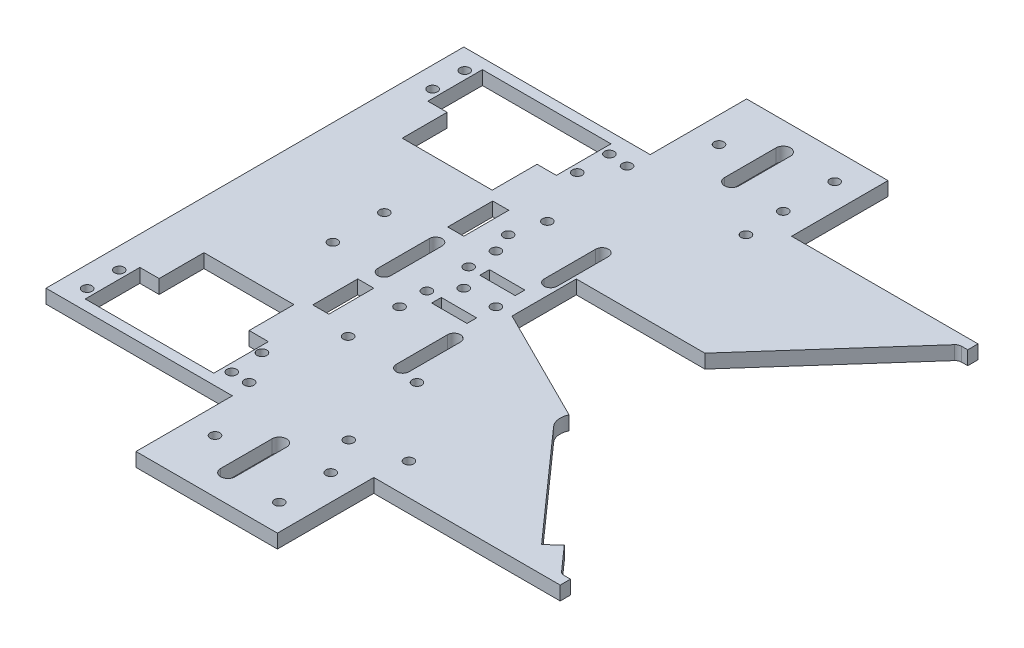
SolidWorks part; units mm, degrees
ref_plane "Front Plane" through (0, 0, 0) normal (0, 0, 1) x (1, 0, 0)
ref_plane "Top Plane" through (0, 0, 0) normal (0, 1, 0) x (1, 0, 0)
ref_plane "Right Plane" through (0, 0, 0) normal (1, 0, 0) x (0, 0, -1)
sketch "Sketch2" plane through (0, 0, 0) normal (0, 1, 0) x (1, 0, 0)
  line L2 (0, 0) -> (0, 65)
  line L3 (0, 65) -> (58, 65)
  line L4 (160, 0) -> (160, 65)
  line L8 (0, 0) -> (160, 0)
  line L9 (102, 65) -> (160, 65)
  line L11 (102, 65) -> (102, 95)
  line L12 (58, 65) -> (58, 95)
  line L13 (58, 95) -> (102, 95)
  dimension "D1" = 65
  dimension "D2" = 160
  dimension "D3" = 44
  dimension "D4" = 30
extrude "Boss-Extrude1" add sketch "Sketch2" along normal blind 4.3
mirror "Mirror1" about plane through (0, 4.3, 0) normal (0, 0, -1) of bodies 101
sketch "Sketch3" plane through (0, 4.3, 0) normal (0, 1, 0) x (1, 0, 0)
  line L0 (160, 61.8) -> (160, -61.8)
  line L1 (120.0126, 20) -> (157.1565, 61.8)
  line L3 (80.0126, 0) -> (80.0126, 20)
  line L4 (80.0126, 20) -> (120.0126, 20)
  line L12 (160, 65) -> (102, 65)
  line L13 (102, 65) -> (102, 95)
  line L15 (102, 95) -> (58, 95)
  line L16 (58, 65) -> (0, 65)
  line L17 (0, 65) -> (0, -65)
  line L18 (0, -65) -> (58, -65)
  line L20 (58, 95) -> (58, 65)
  line L22 (102, -65) -> (160, -65)
  line L23 (160, -65) -> (160, 65)
  line L36 (58, -65) -> (58, -95)
  line L38 (58, -95) -> (102, -95)
  line L39 (58, -95) -> (102, -95)
  line L40 (102, -95) -> (102, -65)
  line L42 (160, -61.8) -> (157.1556, -61.8)
  line L45 (160, 61.8) -> (157.1565, 61.8)
  line L48 (80.0126, 0) -> (120, -20)
  line L49 (120, -20) -> (157.1556, -61.8)
  line M24 (160, -65) -> (160, 65)
  dimension "D2" = 130
  dimension "D3" = 20
  dimension "D4" = 40
  dimension "D1" = 0
extrude "Cut-Extrude1" cut sketch "Sketch3" against normal blind 4.5 contours L48 L49 L1 L4 L3 M24 region at (132.7054, 4.3, -1.1594)
fillet "Fillet1" radius 2 2 edges at (157.1565, 2.15, -61.8) (157.1556, 2.15, 61.8)
ref_axis "Axis1" through (80, 4.3, 95) along (0, 0, -1)
sketch "Sketch4" plane through (0, 4.3, 0) normal (0, 1, 0) x (1, 0, 0)
  line L0 (80, -95) -> (80, 95)
  line L1 (102, -95) -> (58, -95) construction
  line L2 (102, 95) -> (58, 95) construction
ref_plane "Plane2" through (0, 4.3, 0) normal (0, 1, 0) x (1, 0, 0)
sketch "Sketch6" plane through (0, 4.3, 0) normal (0, 1, 0) x (1, 0, 0)
  line L3 (9, -61.8) -> (49, -61.8)
  line L6 (29, -45.8) -> (29, -44.8)
  line L7 (9, -44.8) -> (15, -44.8)
  line L11 (43, -44.8) -> (43, -30.8418)
  line L12 (15, -44.8) -> (15, -30.8418)
  line L13 (15, -30.8418) -> (43, -30.8418)
  line L15 (0, 0) -> (80.0126, 0)
  line L16 (80.0126, 0) -> (120, -20) construction
  line L18 (9, 44.8) -> (15, 44.8)
  line L20 (15, 30.8418) -> (43, 30.8418)
  line L21 (15, 44.8) -> (15, 30.8418)
  line L22 (43, 44.8) -> (43, 30.8418)
  line L25 (15, -45.8) -> (15, -30.8418) construction
  line L27 (9, 61.8) -> (49, 61.8)
  line L30 (4, -61.8) -> (3, -61.8)
  line L31 (0, -61.8) -> (160, -61.8) construction
  line L32 (3, -61.8) -> (4, -61.8)
  line L33 (3, -44.8) -> (3, -62.8) construction
  line L34 (3, -62.8) -> (55, -62.8) construction
  line L35 (55, -44.8) -> (55, -62.8) construction
  line L36 (4, -61.8) -> (54, -61.8) construction
  line L37 (0, 61.8) -> (160, 61.8) construction
  line L38 (54, 61.8) -> (55, 61.8)
  line L39 (54, 61.8) -> (55, 61.8)
  line L40 (43, 44.8) -> (49, 44.8)
  line L41 (4, -45.8) -> (4, -61.8) construction
  line L42 (4, -45.8) -> (54, -45.8) construction
  line L43 (43, -44.8) -> (49, -44.8)
  line L44 (3, -44.8) -> (55, -44.8) construction
  line L45 (29, -45.8) -> (29, -30.8418) construction
  line L46 (43, -45.8) -> (43, -30.8418) construction
  line L47 (54, -45.8) -> (54, -61.8) construction
  line L48 (9, -61.8) -> (49, -61.8)
  line L52 (9, 61.8) -> (9, 44.8)
  line L53 (55, 61.8) -> (54, 61.8)
  line L56 (49, 61.8) -> (49, 44.8)
  line L59 (3, -61.8) -> (4, -61.8)
  line L60 (9, -44.8) -> (9, -61.8)
  line L64 (49, -44.8) -> (49, -61.8)
  dimension "D4" = 1
  dimension "D5" = 14
  dimension "D6" = 14
extrude "Cut-Extrude2" cut sketch "Sketch6" against normal blind 10
sketch "Sketch8" plane through (0, 4.3, 0) normal (0, 1, 0) x (1, 0, 0)
  circle A0 centre (6.5, 58.8) radius 1.5
  circle A1 centre (6.5, 48.8) radius 1.5
  circle A2 centre (51.5, 48.8) radius 1.5
  circle A3 centre (51.5, 58.8) radius 1.5
  circle A4 centre (6.5, -48.7) radius 1.5
  circle A5 centre (6.5, -58.7) radius 1.5
  circle A6 centre (51.5, -58.7) radius 1.5
  circle A7 centre (51, -48.8) radius 1.5
  dimension "D7" = 3
extrude "Cut-Extrude3" cut sketch "Sketch8" against normal blind 10
sketch "Sketch9" plane through (0, 0, 0) normal (0, -1, 0) x (1, 0, 0)
  line L0 (75.75, 70.4) -> (75.75, 86.4)
  line L1 (75.75, -86.4) -> (75.75, -70.4)
  line L2 (80.25, -86.4) -> (80.25, -70.4)
  line L4 (80.25, 70.4) -> (80.25, 86.4)
  circle A0 centre (94, 70.4) radius 1.5
  circle A1 centre (66, 78.4) radius 1.5
  circle A2 centre (66, -78.4) radius 1.5
  circle A3 centre (94, -86.4) radius 1.5
  circle A4 centre (94, 86.4) radius 1.5
  circle A5 centre (94, -70.4) radius 1.5
  arc A6 (75.75, -86.4) -> (80.25, -86.4) centre (78, -86.4) ccw
  arc A7 (80.25, -70.4) -> (75.75, -70.4) centre (78, -70.4) ccw
  arc A10 (75.75, 70.4) -> (80.25, 70.4) centre (78, 70.4) ccw
  arc A12 (80.25, 86.4) -> (75.75, 86.4) centre (78, 86.4) ccw
  dimension "D1" = 3
extrude "Cut-Extrude4" cut sketch "Sketch9" against normal blind 10
sketch "Sketch7" plane through (0, 4.3, 0) normal (0, 1, 0) x (1, 0, 0)
  line L0 (0, 0) -> (80.0126, 0)
  line L1 (0, 65) -> (0, -65) construction
  line L2 (80.0126, 0) -> (80.0126, 20) construction
  line L3 (80, -95) -> (80, 95) construction
  line L4 (64, -9) -> (75, -9)
  line L5 (64, -6) -> (75, -6)
  line L6 (64, -9) -> (64, -6)
  line L7 (75, -9) -> (75, -6)
  line L8 (64, -7.5) -> (75, -7.5)
  line L9 (64, 7.5) -> (75, 7.5)
  line L10 (75, 9) -> (75, 6)
  line L11 (64, 9) -> (64, 6)
  line L12 (64, 6) -> (75, 6)
  line L13 (64, 9) -> (75, 9)
  circle A0 centre (60.0126, -6.5) radius 1.5
  circle A1 centre (60.0126, 6.5) radius 1.5
  dimension "D1" = 3
  dimension "D2" = 6.5
  dimension "D3" = 20
  dimension "D6" = 11
  dimension "D4" = 5
  dimension "D5" = 3
  dimension "D7" = 7.5
sketch "Sketch10" plane through (0, 4.3, 0) normal (0, 1, 0) x (1, 0, 0)
  line L0 (120, -20) -> (156.5589, -61.1287) construction
  line L1 (123.3218, -23.737) -> (149.8964, -53.6334)
  line L2 (116.263, -23.3218) -> (146.1593, -56.9552)
  line L3 (149.8964, -53.6334) -> (146.1593, -56.9552)
  line L4 (120, -20) -> (156.5589, -61.1287) construction
  line L5 (116.263, -23.3218) -> (152.8218, -64.4505) construction
  arc A0 (123.3218, -23.737) -> (116.263, -23.3218) centre (120, -20) ccw
  dimension "D1" = 5
  dimension "D2" = 45
extrude "Cut-Extrude5" cut sketch "Sketch10" against normal blind 10
sketch "Sketch11" plane through (0, 0, 0) normal (0, -1, 0) x (1, 0, 0)
  line L0 (0, 0) -> (80.0126, 0) construction
  line L1 (80, 95) -> (80, -95) construction
  line L2 (80.0126, 0) -> (0, 0)
  line L4 (75, 31.0313) -> (75, 15.0313)
  line L6 (79, 31.0313) -> (79, 15.0313)
  line L7 (79, -31.0313) -> (79, -15.0313)
  line L8 (75, -31.0313) -> (75, -15.0313)
  circle A0 centre (60, 31) radius 1.5
  circle A1 centre (60, 15) radius 1.5
  arc A2 (75, 31.0313) -> (79, 31.0313) centre (77, 31.0313) cw
  arc A3 (75, 15.0313) -> (79, 15.0313) centre (77, 15.0313) ccw
  arc A4 (75, -15.0313) -> (79, -15.0313) centre (77, -15.0313) cw
  arc A5 (75, -31.0313) -> (79, -31.0313) centre (77, -31.0313) ccw
  circle A6 centre (60, -15) radius 1.5
  circle A7 centre (60, -31) radius 1.5
  dimension "D1" = 3
  dimension "D2" = 16
  dimension "D3" = 15
  dimension "D4" = 20
  dimension "D5" = 15
  dimension "D6" = 4
extrude "Cut-Extrude6" cut sketch "Sketch11" against normal blind 10 contours L4 A3 L6 A2 | L8 A5 L7 A4 | A7 | A0 | A1 | A6 region at (77, 0, 23.0313) region at (77, 0, -23.0313) region at (60, 0, -31)
sketch "Sketch12" plane through (0, 0, 0) normal (0, -1, 0) x (-1, 0, 0)
  line L0 (0, 0) -> (-80.0126, 0) construction
  line L3 (-50.2627, -8) -> (-50.2627, 8)
  line L4 (-50.2627, 0) -> (-46.2627, 0)
  line L5 (-46.2627, -8) -> (-46.2627, 8)
  line L6 (0, 0) -> (-46.2627, 0)
  line L7 (0, 65) -> (0, -65) construction
  line L8 (-160, -61.8) -> (0, -61.8) construction
  line L9 (-80.0126, 0) -> (-50.2627, 0)
  line L10 (-80.0126, 0) -> (-115.5281, -17.7634) construction
  line L11 (-80.0126, 0) -> (-80.0126, 20) construction
  line L12 (-58, -65) -> (0, -65) construction
  line L13 (-58, 65) -> (0, 65) construction
  circle A0 centre (-32.2627, -8) radius 1.5
  circle A1 centre (-32.2627, 8) radius 1.5
  arc A2 (-46.2627, 8) -> (-50.2627, 8) centre (-48.2627, 8) ccw
  arc A3 (-50.2627, -8) -> (-46.2627, -8) centre (-48.2627, -8) ccw
  circle A5 centre (-32.2627, -8) radius 1.5 construction
  circle A6 centre (-32.2627, 8) radius 1.5 construction
  dimension "D1" = 3
  dimension "D8" = 8
  dimension "D9" = 8
  dimension "D2" = 8
  dimension "D3" = 14
  dimension "D4" = 4
  dimension "D5" = 61.8
  dimension "D6" = 65
  dimension "D7" = 65
extrude "Cut-Extrude7" cut sketch "Sketch12" against normal blind 10 contours A3 L5 L4 L3 | L4 L5 A2 L3 | A0 | A1 region at (48.2627, 0, 4.7958) region at (48.2627, 0, -4.7958) region at (32.2627, 0, 8) region at (32.2627, 0, -8)
extrude "Cut-Extrude8" cut sketch "Sketch7" against normal blind 9 contours A0 | L4 L7 L5 L6 | L12 L10 L13 L11 | A1
sketch "Sketch13" plane through (0, 4.3, 0) normal (0, 1, 0) x (1, 0, 0)
  line L0 (80.0126, 0) -> (59.0194, 0)
  line L1 (80, -95) -> (80, 95) construction
  circle A0 centre (65, 0) radius 1.5
  circle A1 centre (75, 0) radius 1.5
  dimension "D2" = 3
  dimension "D3" = 5
  dimension "D1" = 10
extrude "Cut-Extrude9" cut sketch "Sketch13" against normal blind 10 contours L0 A0 | L0 A0 | L0 A1 | L0 A1 region at (75, 4.3, 0.6366) region at (75, 4.3, -0.6366) region at (65, 4.3, 0.6366) region at (65, 4.3, -0.6366)
sketch "Sketch14" plane through (0, 4.3, 0) normal (0, 1, 0) x (1, 0, 0)
  circle A0 centre (57.5, 58.3) radius 1.5
  circle A1 centre (94.5, 58.3) radius 1.5
  circle A2 centre (57.5, 21.3) radius 1.5
  circle A3 centre (83.1278, -32.706) radius 1.5
  circle A4 centre (103.0587, -55.1282) radius 1.5
  dimension "D1" = 3
  dimension "D2" = 3
extrude "Cut-Extrude10" cut sketch "Sketch14" against normal blind 10
sketch "Sketch15" plane through (0, 4.3, 0) normal (0, 1, 0) x (1, 0, 0)
  line L1 (46, 28) -> (51, 28)
  line L2 (46, 28) -> (46, 14)
  line L3 (46, 14) -> (51, 14)
  line L4 (51, 28) -> (51, 14)
  line L6 (0, 65) -> (0, -65) construction
  line L7 (80.0126, 0) -> (53.7017, 0)
  line L8 (46, -14) -> (51, -14)
  line L9 (51, -28) -> (51, -14)
  line L10 (46, -28) -> (51, -28)
  line L11 (46, -28) -> (46, -14)
  arc A0 (50.2627, 8) -> (46.2627, 8) centre (48.2627, 8) ccw construction
  arc A1 (46.2627, -8) -> (50.2627, -8) centre (48.2627, -8) ccw construction
  dimension "D1" = 46
  dimension "D2" = 5
  dimension "D3" = 14
  dimension "D4" = 14
  dimension "D5" = 14
  dimension "D6" = 6
  dimension "D7" = 6
extrude "Cut-Extrude11" cut sketch "Sketch15" against normal blind 10 contours L4 L1 L2 L3 | L11 L10 L9 L8 region at (48.5, 4.3, -21) region at (48.5, 4.3, 21)
sketch "Sketch16" plane through (0, 4.3, 0) normal (0, 1, 0) x (1, 0, 0)
  circle A0 centre (88, -58.8) radius 1.5
  circle A1 centre (57, -58.8) radius 1.5
  dimension "D1" = 3
extrude "Cut-Extrude12" cut sketch "Sketch16" against normal blind 10
